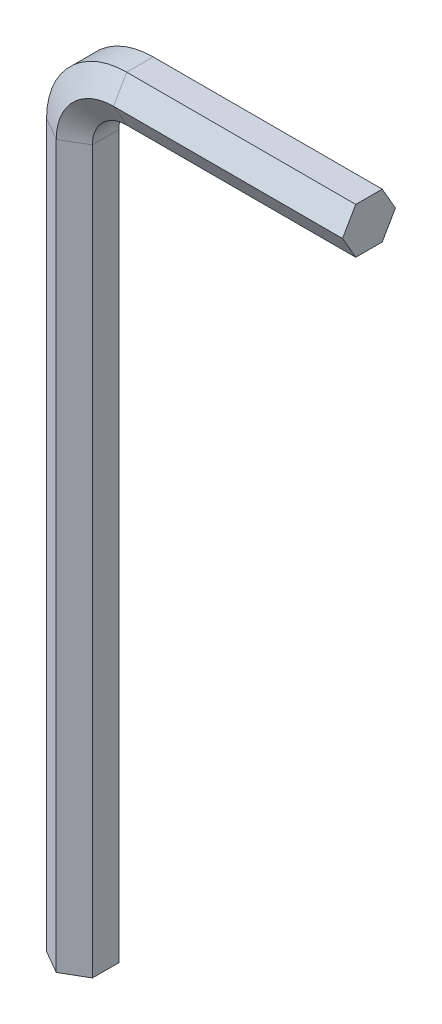
SolidWorks part; units mm, degrees
material "6061-T6 (SS)"
ref_plane "Front Plane" through (0, 0, 0) normal (0, 0, 1) x (1, 0, 0)
ref_plane "Top Plane" through (0, 0, 0) normal (0, 1, 0) x (1, 0, 0)
ref_plane "Right Plane" through (0, 0, 0) normal (1, 0, 0) x (0, 0, -1)
ref_axis "Axis1" through (0, 0, 55) along (0, 0, -1)
sketch "Sketch1" plane through (0, 0, 0) normal (0, 1, 0) x (1, 0, 0)
  line L1 (2, -1.1547) -> (2, 1.1547)
  line L2 (2, 1.1547) -> (0, 2.3094)
  line L3 (0, 2.3094) -> (-2, 1.1547)
  line L4 (-2, 1.1547) -> (-2, -1.1547)
  line L5 (-2, -1.1547) -> (0, -2.3094)
  line L6 (0, -2.3094) -> (2, -1.1547)
  circle A0 centre (0, 0) radius 2 construction
  point P1 (1.2841, 1.9195)
  point P10 (-2.0039, 1.1479)
  dimension "D1" = 4
sketch "Sketch2" plane through (0, 0, 0) normal (0, 0, 1) x (1, 0, 0)
  line L0 (0, 0) -> (0, 63)
  line L1 (5, 68) -> (25, 68)
  arc A0 (0, 63) -> (5, 68) centre (5, 63) cw
  point P6 (0, 68)
  dimension "D3" = 5
  dimension "D1" = 25
  dimension "D2" = 68
sweep "Sweep1" add profiles "Sketch1" path "Sketch2"
